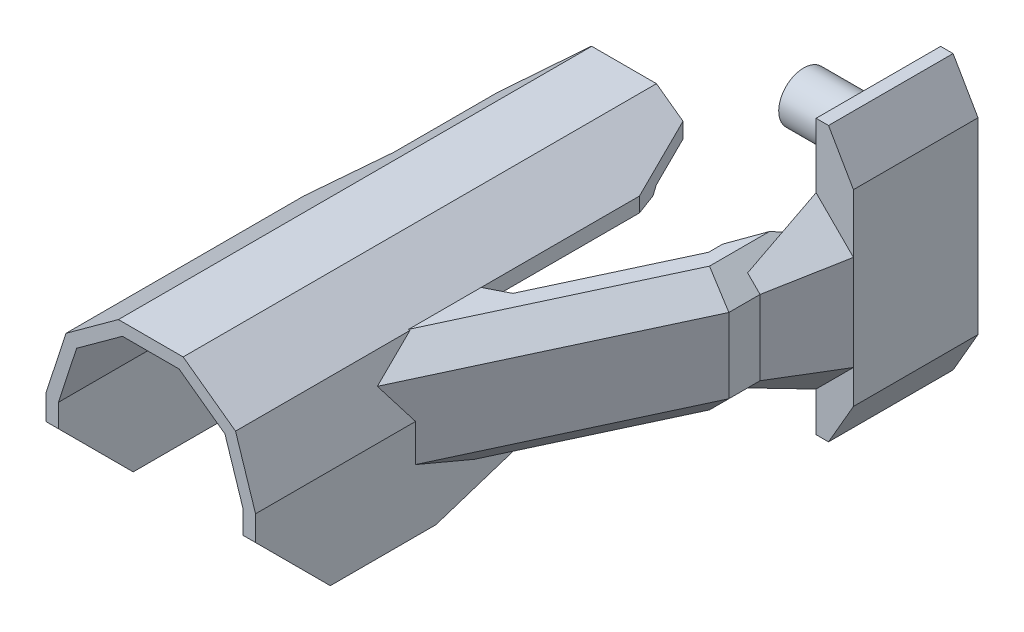
SolidWorks part; units mm, degrees
ref_plane "Plan de face" through (0, 0, 0) normal (0, 0, 1) x (1, 0, 0)
ref_plane "Plan de dessus" through (0, 0, 0) normal (0, 1, 0) x (1, 0, 0)
ref_plane "Plan de droite" through (0, 0, 0) normal (1, 0, 0) x (0, 0, -1)
sketch "Esquisse1" plane through (0, 0, 0) normal (0, 0, 1) x (1, 0, 0)
  line L0 (0, 40) -> (0, 0) construction
  line L1 (-42.0585, 40) -> (42.0585, 40) construction
  line L2 (-42.0585, 40) -> (-42.0585, 0)
  line L3 (-42.0585, 0) -> (-37.0585, 0)
  line L4 (42.0585, 40) -> (42.0585, 0)
  line L5 (42.0585, 40) -> (34.026, 64.7214)
  line L6 (34.026, 64.7214) -> (12.9968, 80)
  line L7 (12.9968, 80) -> (-12.9968, 80)
  line L8 (-12.9968, 80) -> (-34.026, 64.7214)
  line L9 (-34.026, 64.7214) -> (-42.0585, 40)
  line L10 (-42.0585, 40) -> (-34.026, 15.2786) construction
  line L11 (-34.026, 15.2786) -> (-12.9968, 0) construction
  line L12 (-12.9968, 0) -> (12.9968, 0) construction
  line L13 (12.9968, 0) -> (34.026, 15.2786) construction
  line L14 (34.026, 15.2786) -> (42.0585, 40) construction
  line L15 (-37.0585, 5) -> (37.0585, 5) construction
  line L16 (37.0585, 39.2081) -> (37.0585, 5)
  line L17 (37.0585, 39.2081) -> (29.7728, 61.6312)
  line L18 (29.7728, 61.6312) -> (11.3722, 75)
  line L19 (11.3722, 75) -> (-11.3722, 75)
  line L20 (-11.3722, 75) -> (-29.7728, 61.6312)
  line L21 (-29.7728, 61.6312) -> (-37.0585, 39.2081)
  line L22 (-37.0585, 39.2081) -> (-37.0585, 5)
  line L23 (37.0585, 5) -> (37.0585, 0)
  line L24 (-37.0585, 5) -> (-37.0585, 0)
  line L25 (37.0585, 0) -> (42.0585, 0)
  line L26 (-42.0585, 0) -> (42.0585, 0) construction
  line L27 (37.0585, 0) -> (-37.0585, 0) construction
  circle A0 centre (0, 40) radius 40 construction
  point P5 (0, 0)
  dimension "D2" = 35
  dimension "D1" = 5
extrude "Boss.-Extru.1" add sketch "Esquisse1" along normal blind 200
sketch "Esquisse3" plane through (42.0585, 0, 0) normal (1, 0, 0) x (0, 0, -1)
  line L0 (0, 0) -> (0, 40) construction
  line L1 (0, -10) -> (40, -10)
  line L2 (0, -10) -> (0, 100)
  line L3 (0, 100) -> (40, 100)
  line L4 (40, -10) -> (40, 100)
  line L5 (-200, 80) -> (0, 80) construction
  line L6 (-200, 0) -> (0, 0) construction
  dimension "D1" = 20
  dimension "D2" = 10
  dimension "D3" = 40
extrude "Boss.-Extru.2" add sketch "Esquisse3" along normal blind 50 and the other way blind 90
sketch "Esquisse4" plane through (0, 0, 0) normal (0, 0, 1) x (1, 0, 0)
  line L0 (42.0585, 40) -> (42.0585, 15)
  line L1 (42.0585, 15) -> (82.0585, 15)
  line L2 (42.0585, 0) -> (42.0585, 40) construction
  line L3 (34.026, 64.7214) -> (42.0585, 40)
  line L4 (34.026, 64.7214) -> (33.6425, 65)
  line L5 (82.0585, 15) -> (82.0585, 65)
  line L7 (42.0585, 40) -> (82.0585, 40) construction
  line L8 (34.026, 64.7214) -> (12.9968, 80) construction
  line L9 (33.6425, 65) -> (82.0585, 65)
  line L10 (92.0585, 100) -> (92.0585, -10) construction
  dimension "D1" = 25
  dimension "D2" = 50
  dimension "D3" = 10
extrude "Boss.-Extru.3" add sketch "Esquisse4" along normal blind 150
chamfer "Chanfrein1" distance 10 angle 60 2 edges at (92.0585, 100, -20) (92.0585, -10, -20) first distance on face at (22.0585, 100, -20) first distance on face at (22.0585, -10, -20)
chamfer "Chanfrein2" distance 100 angle 25 1 edges at (82.0585, 40, 150) first distance on face at (82.0585, 40, 75)
chamfer "Chanfrein3" distance 10 angle 45 5 edges at (62.0585, 15, 92.8901) (82.0585, 15, 25) (34.5351, 65, 150) (58.7431, 65, 100) (82.0585, 65, 25)
chamfer "Chanfrein4" distance 30 angle 45 2 edges at (-39.5585, 0, 200) (39.5585, 0, 200)
sketch "Esquisse6" plane through (0, 0, 0) normal (0, 0, 1) x (1, 0, 0)
  line L12 (-47.9415, -10) -> (82.0585, -10)
  line L13 (82.0585, -10) -> (92.0585, 7.3205)
  line L14 (92.0585, 7.3205) -> (92.0585, 82.6795)
  line L15 (92.0585, 82.6795) -> (82.0585, 100)
  line L16 (82.0585, 100) -> (-47.9415, 100)
  line L17 (-47.9415, 100) -> (-47.9415, -10)
  line L18 (-47.9415, -10) -> (82.0585, -10)
  line L19 (82.0585, -10) -> (92.0585, 7.3205)
  line L20 (92.0585, 7.3205) -> (92.0585, 82.6795)
  line L21 (92.0585, 82.6795) -> (82.0585, 100)
  line L22 (82.0585, 100) -> (-47.9415, 100)
  line L23 (-47.9415, 100) -> (-47.9415, -10)
  dimension "D1" = 0
extrude "Boss.-Extru.4" add sketch "Esquisse6" along normal blind 10
sketch "Esquisse5" plane through (0, 100, 0) normal (0, 1, 0) x (1, 0, 0)
  line L0 (-47.9415, 40) -> (82.0585, 40) construction
  line L1 (77.0585, 40) -> (-47.9415, 40)
  line L2 (77.0585, 40) -> (77.0585, -10)
  line L3 (77.0585, -10) -> (67.0585, -10)
  line L4 (-47.9415, 40) -> (-47.9415, -10)
  line L5 (67.0585, -10) -> (67.0585, -43.1459)
  line L6 (92.0585, 40) -> (92.0585, -10) construction
  line L7 (67.0585, -43.1459) -> (42.0778, -96.7171)
  line L8 (42.0778, -96.7171) -> (33.6425, -101.0293)
  line L9 (33.6425, -101.0293) -> (33.6425, -10)
  line L10 (33.6425, -130.1664) -> (72.0585, -47.7831) construction
  line L12 (82.0585, -10) -> (-47.9415, -10) construction
  line L14 (33.6425, -130.1664) -> (33.6425, -10) construction
  line L15 (33.6425, -10) -> (12.9968, -10) construction
  line L16 (72.0585, -10) -> (33.6425, -10) construction
  line L19 (33.6425, -10) -> (-47.9415, -10)
  line L20 (67.0585, -10) -> (33.6425, -10) construction
  dimension "D1" = 15
  dimension "D3" = 10
extrude "Enlèv. mat.-Extru.1" cut sketch "Esquisse5" against normal blind 130
sketch "Esquisse7" plane through (77.0585, 0, 0) normal (-1, 0, 0) x (0, 0, 1)
  line L0 (-15, 100) -> (-15, -10) construction
  line L1 (10, 100) -> (-40, 100) construction
  line L2 (-40, -10) -> (10, -10) construction
  circle A0 centre (-15, 80) radius 10
  dimension "D1" = 20
  dimension "D2" = 20
extrude "Boss.-Extru.5" add sketch "Esquisse7" along normal blind 30
chamfer "Chanfrein5" distance 10 angle 70 8 edges at (74.5585, 62.5, 10) (79.5585, 22.5, 10) (82.0585, 40, 10) (69.5585, 65, 10) (79.5585, 57.5, 10) (67.0585, 40, 10) (69.5585, 15, 10) (74.5585, 17.5, 10)
sketch "Esquisse8" plane through (0, 0, 0) normal (0, 1, 0) x (1, 0, 0)
  line L0 (-23.5114, -10) -> (-23.5114, -78.892)
  line L1 (-12.9968, -10) -> (-34.026, -10) construction
  line L2 (-23.5114, -78.892) -> (-42.0585, -124.0087)
  line L3 (-42.0585, -200) -> (-42.0585, -10) construction
  line L4 (-42.0585, -124.0087) -> (-42.0585, -10)
  line L5 (-42.0585, -10) -> (-23.5114, -10)
extrude "Enlèv. mat.-Extru.2" cut sketch "Esquisse8" along normal blind 130
chamfer "Chanfrein6" distance 10 angle 70 4 edges at (-23.5114, 69.2705, 10) (33.6425, 57.3607, 10) (33.6425, 49.7214, 55.5147) (39.5585, 0, 98.005) first distance on face at (5.5594, 69.4326, 10) first distance on face at (33.4913, 50.1869, 103.3854) first distance on face at (38.7093, 31.1162, 98.4391)
